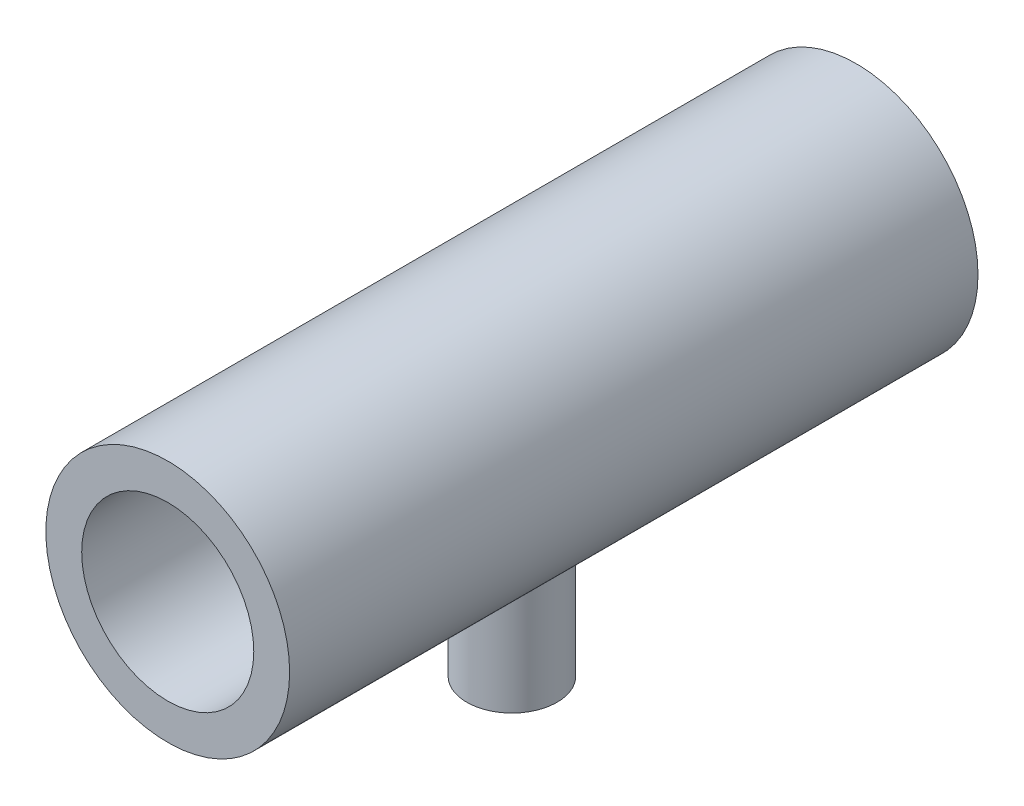
SolidWorks part; units mm, degrees
material "Silicon Rubber"
ref_plane "X-Y Datum" through (0, 0, 0) normal (0, 0, 1) x (1, 0, 0)
ref_plane "X-Z Datum" through (0, 0, 0) normal (0, 1, 0) x (1, 0, 0)
ref_plane "Y-Z Datum" through (0, 0, 0) normal (1, 0, 0) x (0, 0, -1)
sketch3d "3DSketch1"
  line L0 (0, 0, 0) -> (0, 0, 76.2)
  dimension "D1" = 76.2
sweep "Sweep1" add path "3DSketch1" circular profile diameter 26.9875 parameters "D3"=26.9875
sweep "Cut-Sweep1" cut path "3DSketch1<2>" circular profile diameter 19.05 parameters "D3"=19.05
sketch3d "3DSketch1<2>" same geometry as "3DSketch1"
sketch3d "3DSketch2"
  circle A0 centre (0, 0, 50.8) radius 9.525 construction
  circle A1 centre (0, 0, 25.4) radius 9.525 construction
  circle A2 centre (0, 0, 76.2) radius 9.525 construction
  point P4 (0, 0, 15.875)
  point P6 (0, 0, 66.675)
  point P10 (0, 0, 41.275)
  dimension "D1" = 25.4
  dimension "D2" = 25.4
ref_plane "Plane1" through (0, -13.4937, 0) normal (0, -1, 0) x (-1, 0, 0)
sketch "Sketch2" plane through (0, -13.4937, 0) normal (0, -1, 0) x (-1, 0, 0)
  line L0 (13.4937, -76.2) -> (13.4937, 0) construction
  line L1 (13.4937, 0) -> (-13.4937, 0) construction
  line L2 (13.4937, -76.2) -> (13.4937, 0) construction
  line L3 (13.4937, 0) -> (-13.4937, 0) construction
  line L4 (-13.4937, -76.2) -> (13.4937, -76.2) construction
  line L5 (-13.4937, -76.2) -> (13.4937, -76.2) construction
  line L6 (0, -76.2) -> (0, 0) construction
  circle A0 centre (0, -38.1) radius 5
  dimension "D1" = 10
extrude "Boss-Extrude2" add sketch "Sketch2" along normal blind 12.7 and the other way blind 2.54
sketch "Sketch3" plane through (0, -26.1937, 0) normal (0, -1, 0) x (1, 0, 0)
  circle A1 centre (0, 38.1) radius 5
  circle A2 centre (0, 38.1) radius 5 construction
  circle A3 centre (0, 38.1) radius 3.73
  dimension "D1" = 0
  dimension "D2" = 1.27
extrude "Cut-Extrude1" cut sketch "Sketch3" against normal up to next
sketch3d "3DSketch3"
  circle A1 centre (0, -19.8438, 38.1) radius 3.73 construction
  circle A2 centre (0, -26.1937, 38.1) radius 3.73 construction
  point P4 (0, -23.5737, 38.1)
  point P6 (0, -29.9237, 38.1)
  dimension "D1" = 6.35
